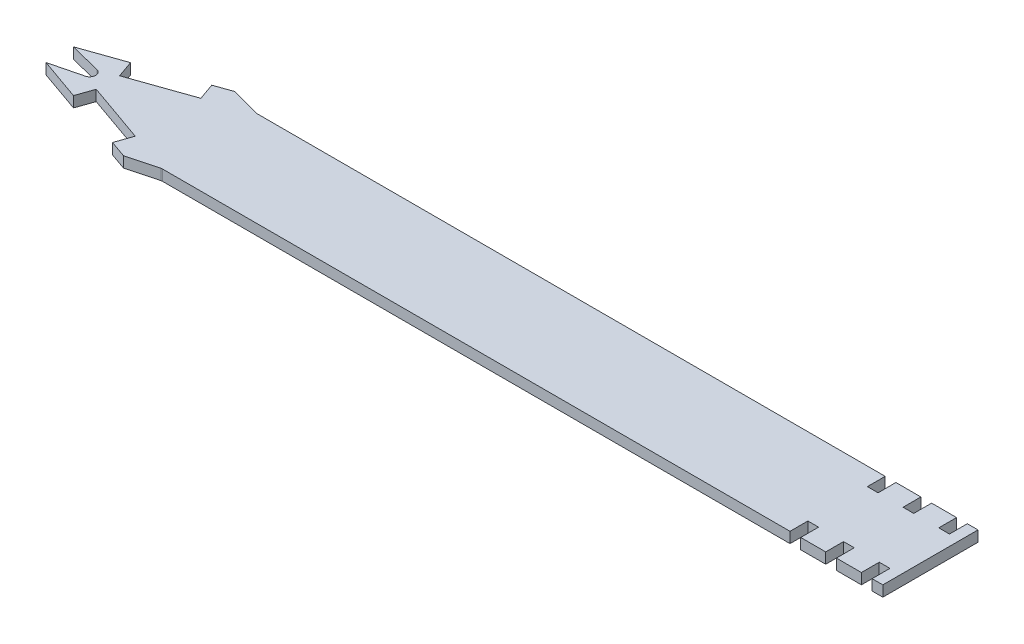
SolidWorks part; units mm, degrees
ref_plane "Front Plane" through (0, 0, 0) normal (0, 0, 1) x (1, 0, 0)
ref_plane "Top Plane" through (0, 0, 0) normal (0, 1, 0) x (1, 0, 0)
ref_plane "Right Plane" through (0, 0, 0) normal (1, 0, 0) x (0, 0, -1)
sketch "Sketch1" plane through (0, 0, 0) normal (0, 1, 0) x (1, 0, 0)
  line L0 (-450, 300) -> (-400, 300)
  line L1 (-400, 300) -> (-200, 250)
  line L2 (-200, 250) -> (200, 250) construction
  line L3 (200, 250) -> (600, 40) construction
  line L4 (600, 40) -> (1200, 40)
  line L5 (-450, -300) -> (-400, -300)
  line L6 (-400, -300) -> (-200, -250)
  line L7 (-200, -250) -> (200, -250) construction
  line L8 (200, -250) -> (600, -40) construction
  line L9 (600, -40) -> (1200, -40)
  line L10 (600, 40) -> (600, -40) construction
  line L11 (200, -250) -> (200, 250) construction
  line L12 (-200, 250) -> (-200, -250) construction
  line L13 (-400, -300) -> (-400, 300) construction
  line L14 (0, 0) -> (200, 0) construction
  line L15 (0, 250) -> (0, 0) construction
  line L16 (1200, 40) -> (1200, -40)
  line L17 (-450, 300) -> (-450, -300)
  line L18 (600, 0) -> (200, 0) construction
  line L19 (-450, 0) -> (-400, 0) construction
  line L20 (-400, 0) -> (-200, 0) construction
  line L21 (-200, 0) -> (0, 0) construction
  line L22 (-200, 250) -> (600, 40)
  line L23 (600, -40) -> (-200, -250)
  dimension "D1" = 600
  dimension "D2" = 200
  dimension "D3" = 50
  dimension "D4" = 400
  dimension "D5" = 500
  dimension "D6" = 80
  dimension "D7" = 600
  dimension "D8" = 400
extrude "Boss-Extrude1" add sketch "Sketch1" along normal blind 15
sketch "Sketch2" plane through (0, 0, 0) normal (0, 0, 1) x (1, 0, 0)
  line L0 (-450, 0) -> (-450, -40)
  line L1 (-450, -40) -> (-400, -40)
  line L2 (-400, -40) -> (-400, 0)
  line L3 (-400, 0) -> (-200, 0) construction
  line L4 (-400, 0) -> (-450, 0)
  line L5 (-440, -15) -> (-440, -40)
  line L6 (-410, -15) -> (-410, -40)
  line L7 (-425, 0) -> (-425, -15) construction
  circle A0 centre (-425, -15) radius 15
  dimension "D1" = 30
  dimension "D2" = 40
extrude "Boss-Extrude2" add sketch "Sketch2" along normal up to surface and the other way up to surface contours L4 L7 A0 L6 L1 L2 | L7 L4 L0 L1 L5 A0 region at (-444.1006, -18.2067, 0) region at (-405.8994, -18.2067, 0) up to face at (-425, 7.5, 300) other way up to face at (-425, 7.5, -300)
sketch "Sketch4" plane through (0, 0, 0) normal (0, 1, 0) x (1, 0, 0)
  line L0 (-450, 230) -> (-400, 230)
  line L1 (-450, 300) -> (-450, -300) construction
  line L2 (-400, 230) -> (-150, 167.5)
  line L3 (-150, 167.5) -> (-150, -167.5)
  line L4 (-150, -167.5) -> (-400, -230)
  line L5 (-400, -230) -> (-450, -230)
  line L6 (-400, 230) -> (-400, -230) construction
  line L7 (-200, 250) -> (-200, -250) construction
  line L9 (-200, 0) -> (-150, 0) construction
  line L10 (-400, -230) -> (-400, -300) construction
  line L11 (-400, -300) -> (-200, -250) construction
  line L12 (-450, 230) -> (-450, -230)
  line L14 (-200, 250) -> (-400, 300) construction
  line L15 (-100, 155) -> (-100, -155)
  line L16 (-100, -155) -> (520, 0)
  line L17 (520, 0) -> (-100, 155)
  line L18 (520, 0) -> (-100, 0) construction
  dimension "D1" = 460
  dimension "D2" = 300
  dimension "D3" = 50
extrude "Cut-Extrude2" cut sketch "Sketch4" against normal through all both and the other way through all
sketch "Sketch5" plane through (0, 0, 0) normal (1, 0, 0) x (0, 0, -1)
  line L0 (-300, 0) -> (-230, 0) construction
  line L1 (-285, 0) -> (-245, 0)
  line L2 (-285, 0) -> (-285, -40)
  line L3 (-285, -40) -> (-245, -40)
  line L4 (-245, 0) -> (-245, -40)
  line L5 (-300, -40) -> (-230, -40) construction
  line L6 (230, 0) -> (300, 0) construction
  line L7 (245, 0) -> (285, 0)
  line L8 (245, 0) -> (245, -40)
  line L9 (245, -40) -> (285, -40)
  line L10 (285, 0) -> (285, -40)
  line L11 (230, -40) -> (300, -40) construction
  line L12 (-300, 0) -> (-300, -40) construction
  line L13 (230, -40) -> (230, 0) construction
  line L14 (300, 0) -> (300, -40) construction
  dimension "D1" = 15
  dimension "D2" = 15
  dimension "D3" = 15
  dimension "D4" = 15
extrude "Cut-Extrude3" cut sketch "Sketch5" against normal through all
sketch "Sketch7" plane through (1200, 0, 0) normal (1, 0, 0) x (0, 0, -1)
  line L1 (-40, 15) -> (-87.5, 50)
  line L2 (-87.5, 50) -> (-87.5, 88.7)
  line L3 (-87.5, 88.7) -> (87.5, 88.7)
  line L4 (87.5, 88.7) -> (87.5, 50)
  line L5 (87.5, 50) -> (40, 15)
  line L7 (-40, 15) -> (40, 15)
  line L8 (-20, 50) -> (-20, 88.7)
  line L9 (87.5, 50) -> (-87.5, 50) construction
  line L10 (0, 88.7) -> (0, 50) construction
  line L11 (-20, 88.7) -> (20, 88.7)
  line L12 (0, 50) -> (0, 0) construction
  line L13 (20, 88.7) -> (20, 50)
  line L14 (-73, 88.7) -> (-63, 88.7)
  line L15 (-73, 88.7) -> (-73, 63.2)
  line L16 (-73, 63.2) -> (-63, 63.2)
  line L17 (-63, 88.7) -> (-63, 63.2)
  line L18 (48.5, 88.7) -> (58.5, 88.7)
  line L19 (48.5, 88.7) -> (48.5, 63.2)
  line L20 (48.5, 63.2) -> (58.5, 63.2)
  line L21 (58.5, 88.7) -> (58.5, 63.2)
  circle A0 centre (0, 50) radius 20
  line M14 (40, 15) -> (-40, 15)
  dimension "D3" = 40
  dimension "D1" = 175
  dimension "D2" = 50
  dimension "D4" = 25.5
  dimension "D5" = 10
  dimension "D6" = 63
  dimension "D7" = 48.5
  dimension "D8" = 38.7
extrude "Boss-Extrude4" add sketch "Sketch7" against normal blind 75 contours L3 L21 L20 L19 L17 L16 L15 L2 L1 L5 L4 M14 region at (1200, 34.0287, 62.6236)
sketch "Sketch8" plane through (0, 0, 0) normal (0, 0, 1) x (1, 0, 0)
  line L0 (1125, 88.7) -> (1200, 88.7) construction
  line L1 (1140, 88.7) -> (1185, 88.7)
  line L2 (1140, 88.7) -> (1140, 15)
  line L3 (1140, 15) -> (1185, 15)
  line L4 (1185, 88.7) -> (1185, 15)
  line L5 (1125, 15) -> (1200, 15) construction
  line L6 (1125, 50) -> (1125, 88.7) construction
  line L7 (1200, 50) -> (1200, 88.7) construction
  line L8 (1155, 88.7) -> (1170, 88.7) construction
  line L9 (1155, 88.7) -> (1170, 88.7)
  line L10 (1155, 88.7) -> (1155, 15)
  line L11 (1155, 15) -> (1170, 15)
  line L12 (1170, 88.7) -> (1170, 15)
  line L15 (1162.5, 50) -> (1162.5, 88.7) construction
  line L16 (1125, 50) -> (1200, 50) construction
  line L17 (1155, 88.7) -> (1170, 88.7) construction
  dimension "D1" = 15
  dimension "D2" = 15
  dimension "D3" = 15
extrude "Cut-Extrude4" cut sketch "Sketch8" against normal through all both and the other way through all contours L10 L1 L2 L3 | L1 L12 L3 L4 region at (1147.5, 51.85, 0) region at (1177.5, 51.85, 0)
fillet "Fillet1" radius 5 53 edges at (1192.5, 50, 87.5) (1162.5, 50, 87.5) (1132.5, 50, 87.5) (1192.5, 50, -87.5) (1162.5, 50, -87.5) (1132.5, 50, -87.5) (1192.5, 88.7, -87.5) (1162.5, 88.7, -87.5) (1132.5, 88.7, -87.5) (1132.5, 88.7, -58.5) (1162.5, 88.7, -58.5) (1192.5, 88.7, -58.5) (1192.5, 88.7, -48.5) (1162.5, 88.7, -48.5) (1132.5, 88.7, -48.5) (1192.5, 88.7, -20) (1162.5, 88.7, -20) (1132.5, 88.7, -20) (1192.5, 88.7, 63) (1162.5, 88.7, 63) (1132.5, 88.7, 63) (1132.5, 88.7, 87.5) (1162.5, 88.7, 87.5) (1192.5, 88.7, 87.5) (1192.5, 88.7, 73) (1162.5, 88.7, 73) (1132.5, 88.7, 73) (1192.5, 88.7, 20) (1162.5, 88.7, 20) (1132.5, 88.7, 20) (600, 7.5, 40) (600, 7.5, -40) (520, 7.5, 0) (-440, -40, -292.5) (-440, -40, -237.5) (-400, -40, -292.5) (-400, -40, -237.5) (-450, -40, -237.5) (-410, -40, -237.5) (-450, -40, -292.5) (-410, -40, -292.5) (-150, 7.5, 167.5) (-100, 7.5, 155) (-150, 7.5, -167.5) (-100, 7.5, -155) (-450, -40, 237.5) (-410, -40, 237.5) (-440, -40, 237.5) (-400, -40, 237.5) (-450, -40, 292.5) (-440, -40, 292.5) (-400, -40, 292.5) (-410, -40, 292.5)
sketch "Sketch9" plane through (0, 0, 0) normal (0, 1, 0) x (1, 0, 0)
  line L35 (-450, -300) -> (-400, -300) construction
  line L36 (-425, -300) -> (-425, -285) construction
  line L37 (-450, 0) -> (0, 0) construction
  line L38 (-437.5, -300) -> (-412.5, -300)
  line L39 (-437.5, -300) -> (-437.5, -285)
  line L56 (1140, -40) -> (1140, -85.466) construction
  line L57 (1200, -40) -> (1185, -40)
  line L58 (1200, -40) -> (1200, -25)
  line L59 (1200, -25) -> (1185, -25)
  line L60 (1185, -40) -> (1185, -25)
  line L61 (1200, 40) -> (1185, 40)
  line L62 (1200, 40) -> (1200, 25)
  line L63 (1200, 25) -> (1185, 25)
  line L64 (1185, 40) -> (1185, 25)
  line L65 (1170, 40) -> (1155, 40)
  line L66 (1170, 40) -> (1170, 25)
  line L67 (1170, 25) -> (1155, 25)
  line L68 (1155, 40) -> (1155, 25)
  line L69 (1140, 40) -> (1125, 40)
  line L70 (1140, 40) -> (1140, 25)
  line L71 (1140, 25) -> (1125, 25)
  line L72 (1125, 40) -> (1125, 25)
  line L73 (1125, -40) -> (1140, -40)
  line L74 (1125, -40) -> (1125, -25)
  line L75 (1125, -25) -> (1140, -25)
  line L76 (1140, -40) -> (1140, -25)
  line L77 (1155, -40) -> (1170, -40)
  line L78 (1155, -40) -> (1155, -25)
  line L79 (1155, -25) -> (1170, -25)
  line L80 (1170, -40) -> (1170, -25)
  line L81 (600.6453, -40) -> (1200, -40) construction
  line L82 (1200, 40) -> (600.6453, 40) construction
  line L83 (1140, 40) -> (1125, 40) construction
  line L84 (1125, 85.466) -> (1125, 40) construction
  line L85 (1140, -25) -> (1155, -25) construction
  line L86 (1170, -25) -> (1185, -25) construction
  line L87 (1185, 25) -> (1170, 25) construction
  line L88 (1155, 25) -> (1140, 25) construction
  line L89 (-437.5, -285) -> (-412.5, -285)
  line L90 (-412.5, -300) -> (-412.5, -285)
  line L92 (-410, -230) -> (-440, -230) construction
  line L93 (-437.5, -230) -> (-412.5, -230)
  line L94 (-437.5, -230) -> (-437.5, -245)
  line L95 (-437.5, -245) -> (-412.5, -245)
  line L96 (-412.5, -230) -> (-412.5, -245)
  line L97 (-425, -245) -> (-400, -245) construction
  line L98 (-425, -285) -> (-425, -245) construction
  line L99 (-425, 285) -> (-425, 245) construction
  line L100 (-425, 300) -> (-425, 285) construction
  line L101 (-450, 300) -> (-400, 300) construction
  line L102 (-412.5, 230) -> (-412.5, 245)
  line L103 (-437.5, 245) -> (-412.5, 245)
  line L104 (-437.5, 230) -> (-437.5, 245)
  line L105 (-437.5, 230) -> (-412.5, 230)
  line L106 (-412.5, 300) -> (-412.5, 285)
  line L107 (-437.5, 285) -> (-412.5, 285)
  line L108 (-437.5, 300) -> (-437.5, 285)
  line L109 (-437.5, 300) -> (-412.5, 300)
  dimension "D1" = 15
  dimension "D2" = 25
  dimension "D3" = 15
extrude "Cut-Extrude5" cut sketch "Sketch9" against normal through all both and the other way through all
sketch "Sketch10" plane through (0, 0, 0) normal (0, 0, 1) x (1, 0, 0)
  line L1 (-450, 15) -> (1200, 15)
  line L2 (-450, 15) -> (-450, 0)
  line L3 (-450, 0) -> (1200, 0)
  line L4 (1200, 15) -> (1200, 0)
  line L5 (-450, 15) -> (-450, -35) construction
  line L6 (-486.0808, 110.0266) -> (1242.84, 110.0266)
  line L7 (-486.0808, 110.0266) -> (-486.0808, -68.8272)
  line L8 (-486.0808, -68.8272) -> (1242.84, -68.8272)
  line L9 (1242.84, 110.0266) -> (1242.84, -68.8272)
  dimension "D1" = 15
extrude "Cut-Extrude6" cut sketch "Sketch10" against normal through all both and the other way through all
sketch "Sketch11" plane through (0, 0, 0) normal (0, 1, 0) x (1, 0, 0)
  line L1 (-450, 300) -> (-437.5, 300) construction
  line L7 (-93.7873, -153.4468) -> (500.5971, -4.8507) construction
  line L8 (-200, -250) -> (599.3758, -40.1638) construction
  line L18 (-450, -300) -> (1200, -300)
  line L19 (-450, -300) -> (-450, 300)
  line L20 (-450, 300) -> (1200, 300)
  line L21 (1200, -300) -> (1200, 300)
  line L26 (574.4681, -46.7021) -> (600.6453, -40)
  line L27 (600.6453, -40) -> (500.5971, -4.8507)
  line L28 (500.5971, -4.8507) -> (474.1575, -11.4606)
  line L29 (574.4681, -46.7021) -> (474.1575, -11.4606)
  line L30 (560.3161, -41.7302) -> (565.288, -27.5782)
  line L31 (509.7772, -23.9747) -> (514.7492, -9.8227)
  line L32 (-253.7911, 0) -> (928.7767, 0) construction
  line L33 (509.7772, 23.9747) -> (514.7492, 9.8227)
  line L34 (560.3161, 41.7302) -> (565.288, 27.5782)
  line L35 (574.4681, 46.7021) -> (474.1575, 11.4606)
  line L36 (600.6453, 40) -> (500.5971, 4.8507)
  line L37 (600.6453, 40) -> (574.4681, 46.7021)
  line L38 (500.5971, 4.8507) -> (474.1575, 11.4606)
  line L39 (1200, 25) -> (1200, -25) construction
  line L40 (1200, -40) -> (600.6453, -40)
  line L41 (1200, -40) -> (1200, 40)
  line L42 (1200, 40) -> (600.6453, 40)
  line L43 (600.6453, -40) -> (600.6453, 40)
  dimension "D6" = 15
  dimension "D7" = 15
  dimension "D8" = 15
sketch "Sketch12" plane through (0, 0, 0) normal (0, 1, 0) x (1, 0, 0)
  line L0 (441.5362, 0) -> (600.6453, 55.8988)
  line L1 (-450, -300) -> (600.6453, -300)
  line L2 (-450, -300) -> (-450, 300)
  line L3 (-450, 300) -> (600.6453, 300)
  line L4 (600.6453, -300) -> (600.6453, 300)
  line L5 (-200253.7911, 0) -> (200928.7767, 0) construction
  line L6 (574.4681, 46.7021) -> (474.1575, 11.4606) construction
  line L7 (441.5362, 0) -> (600.6453, -55.8988)
  line L8 (574.4681, -46.7021) -> (474.1575, -11.4606) construction
  line L9 (600.6453, -40) -> (500.5971, -4.8507)
  line L10 (500.5971, -4.8507) -> (474.1575, -11.4606)
  line L11 (514.7492, -9.8227) -> (509.7772, -23.9747)
  line L12 (560.3161, -41.7302) -> (565.288, -27.5782)
  line L13 (600.6453, -40) -> (574.4681, -46.7021)
  line L14 (574.4681, 46.7021) -> (600.6453, 40)
  line L15 (600.6453, 40) -> (500.5971, 4.8507)
  line L16 (500.5971, 4.8507) -> (474.1575, 11.4606)
  line L17 (514.7492, 9.8227) -> (509.7772, 23.9747)
  line L18 (560.3161, 41.7302) -> (565.288, 27.5782)
extrude "Cut-Extrude8" cut sketch "Sketch12" along normal through all contours L7 L0 L4 L3 L2 L1 | L7 L12 L9 L11 | L18 L0 L17 L15 region at (68.5639, 0, 0) region at (537.5326, 0, -25.7764) region at (537.5326, 0, 25.7764)
sketch "Sketch13" plane through (0, 15, 0) normal (0, 1, 0) x (1, 0, 0)
  line L0 (1200, 25) -> (1200, -25) construction
  line L1 (1125, 40) -> (1128, 40)
  line L2 (1125, 40) -> (1125, -40)
  line L3 (1125, -40) -> (1128, -40)
  line L4 (1128, 40) -> (1128, -40)
  line L5 (1137, -40) -> (1158, -40)
  line L6 (1137, -40) -> (1137, 40)
  line L7 (1137, 40) -> (1158, 40)
  line L8 (1158, -40) -> (1158, 40)
  line L9 (1167, 40) -> (1188, 40)
  line L10 (1167, 40) -> (1167, -40)
  line L11 (1167, -40) -> (1188, -40)
  line L12 (1188, 40) -> (1188, -40)
  line L13 (1197, 40) -> (1200, 40)
  line L14 (1197, 40) -> (1197, -40)
  line L15 (1197, -40) -> (1200, -40)
  line L16 (1200, 40) -> (1200, -40) construction
  line L17 (1128, 0) -> (1137, 0) construction
  line L18 (1158, 0) -> (1167, 0) construction
  line L19 (1188, 0) -> (1197, 0) construction
  line L20 (1125, 25) -> (1128, 25) construction
  line L21 (1140, 25) -> (1125, 25) construction
  line L22 (1140, 25) -> (1137, 25) construction
  line L23 (600.6453, -40) -> (1125, -40) construction
  line L24 (1200, 40) -> (1200, -40)
  line L25 (1200, 40) -> (1206, 40)
  line L26 (1200, 40) -> (1200, -40)
  line L27 (1200, -40) -> (1206, -40)
  line L28 (1206, 40) -> (1206, -40)
  line M35 (1125, -40) -> (1125, -25)
  line M36 (1125, -25) -> (1140, -25)
  line M37 (1140, -25) -> (1140, -40)
  line M38 (1140, -40) -> (1155, -40)
  line M39 (1155, -40) -> (1155, -25)
  line M40 (1155, -25) -> (1170, -25)
  line M41 (1170, -25) -> (1170, -40)
  line M42 (1170, -40) -> (1185, -40)
  line M43 (1185, -40) -> (1185, -25)
  line M44 (1185, -25) -> (1200, -25)
  line M45 (1200, -25) -> (1200, 25)
  line M46 (1200, 25) -> (1185, 25)
  line M47 (1185, 25) -> (1185, 40)
  line M48 (1185, 40) -> (1170, 40)
  line M49 (1170, 40) -> (1170, 25)
  line M50 (1170, 25) -> (1155, 25)
  line M51 (1155, 25) -> (1155, 40)
  line M52 (1155, 40) -> (1140, 40)
  line M53 (1140, 40) -> (1140, 25)
  line M54 (1140, 25) -> (1125, 25)
  line M55 (1125, 25) -> (1125, 40)
  dimension "D1" = 9
  dimension "D2" = 9
extrude "Boss-Extrude5" add sketch "Sketch13" against normal up to surface (15 mm away) contours L4 L2 M54 M36 | L8 L6 M40 M50 M51 M52 M53 M54 M36 M37 M38 M39 | L12 L10 M46 M47 M48 M49 M50 M40 M41 M42 M43 M44 | L28 L25 L24 L27 M45 | L14 M46 M44 M45 | L24 L13 L14 M46 | L24 L14 L15 M44 | L12 L11 M44 M43 | L10 L11 M41 M40 | L5 L8 M40 M39 | L6 L5 M37 M36 | L4 L3 M36 M35 | L4 L1 M55 M54 | L7 L6 M54 M53 | L8 L7 M50 M51 | L9 L10 M50 M49 | L12 L9 M47 M46 region at (1126.5, 15, -32.5) region at (1126.5, 15, 0) region at (1126.5, 15, 32.5) region at (1147.5, 15, 0) region at (1138.5, 15, -32.5) region at (1138.5, 15, 32.5) region at (1156.5, 15, -32.5) region at (1156.5, 15, 32.5) region at (1177.5, 15, 0) region at (1168.5, 15, -32.5) region at (1168.5, 15, 32.5) region at (1186.5, 15, -32.5) region at (1186.5, 15, 32.5) region at (1198.5, 15, 0) region at (1198.5, 15, -32.5) region at (1198.5, 15, 32.5) region at (1203, 15, 0) up to face at (882.5631, 0, 0)
sketch "Sketch14" plane through (0, 0, 0) normal (0, 0, 1) x (1, 0, 0)
  line L1 (474.1575, 15) -> (1206, 15)
  line L2 (474.1575, 15) -> (474.1575, 9)
  line L3 (474.1575, 9) -> (1206, 9)
  line L4 (1206, 15) -> (1206, 9)
  line L5 (1206, 0) -> (1197, 0) construction
  line L6 (1206, 0) -> (1206, 15) construction
  point P5 (1206, 9)
  point P10 (1211.9904, 9)
  point P11 (1220.3671, 9)
  dimension "D1" = 9
extrude "Cut-Extrude10" cut sketch "Sketch14" against normal through all both and the other way through all
